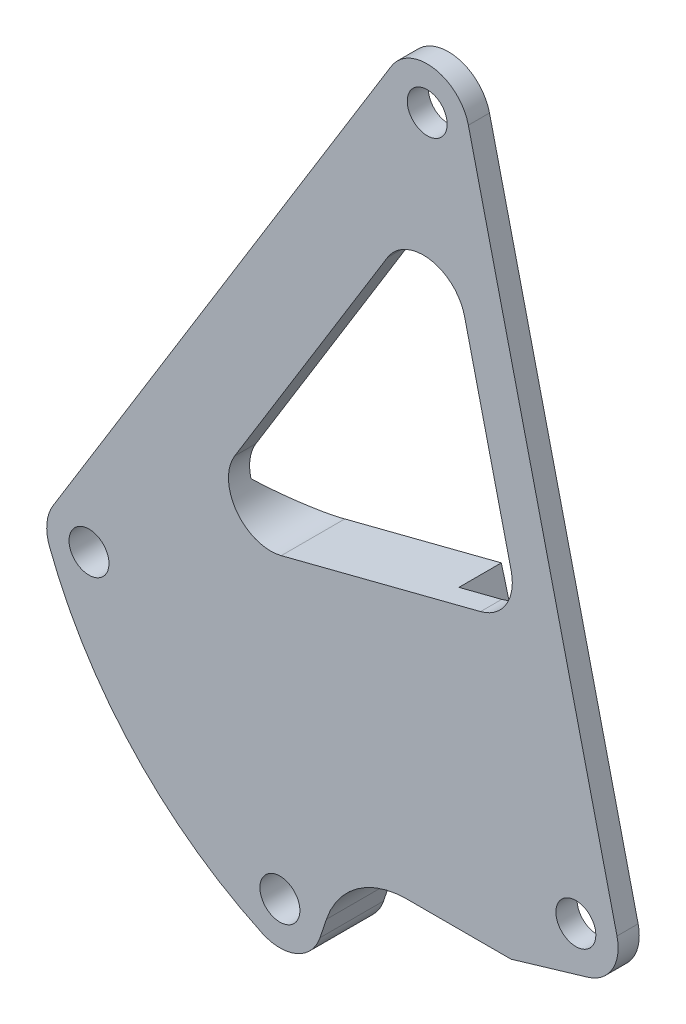
SolidWorks part; units mm, degrees
ref_plane "Front Plane" through (0, 0, 0) normal (0, 0, 1) x (1, 0, 0)
ref_plane "Top Plane" through (0, 0, 0) normal (0, 1, 0) x (1, 0, 0)
ref_plane "Right Plane" through (0, 0, 0) normal (1, 0, 0) x (0, 0, -1)
sketch "Sketch1" plane through (0, 0, 0) normal (0, 0, 1) x (1, 0, 0)
  circle A0 centre (0, 0) radius 3
  circle A1 centre (0, 0) radius 6.35
  dimension "D1" = 6
  dimension "D2" = 12.7
extrude "Boss-Extrude1" add sketch "Sketch1" along normal mid plane 6.3739
sketch "Sketch2" plane through (0, 0, 3.1869) normal (0, 0, 1) x (1, 0, 0)
  circle A0 centre (-28.6728, 30.8026) radius 3
  circle A1 centre (-28.6728, 30.8026) radius 6.35
  circle A2 centre (0, 0) radius 6.35 construction
  circle A3 centre (0, 0) radius 3 construction
  dimension "D1" = 28.6728
  dimension "D2" = 30.8026
extrude "Boss-Extrude2" add sketch "Sketch2" against normal blind 6.3739 separate body
sketch "Sketch3" plane through (0, 0, 0) normal (0, 0, 1) x (1, 0, 0)
  line L0 (-30.2527, 36.9529) -> (23.7075, 50.8147)
  line L1 (6.0215, -2.0158) -> (23.7075, 50.8147)
  line L2 (-28.6728, 30.8026) -> (0, 0) construction
  arc A0 (-34.6046, 28.5363) -> (-2.6848, -5.7545) centre (23.7075, 50.8147) ccw
  circle A1 centre (-28.6728, 30.8026) radius 6.35 construction
  circle A2 centre (0, 0) radius 6.35 construction
  circle A4 centre (-28.6728, 30.8026) radius 6.35
  arc A5 (-30.2527, 36.9529) -> (-34.6046, 28.5363) centre (-28.6728, 30.8026) ccw
  circle A6 centre (0, 0) radius 6.35
  arc A7 (-2.6848, -5.7545) -> (6.0215, -2.0158) centre (0, 0) ccw
  point P7 (5.1543, 3.7089)
  point P10 (22.8471, 50.0138)
  point P11 (22.8471, 50.0138)
  point P14 (-30.4587, 36.8963)
  dimension "D1" = 0
  dimension "D3" = 51.9755
  dimension "D2" = 0
extrude "Boss-Extrude3" add sketch "Sketch3" along normal mid plane 6.3739 contours L0 L1 A7 A0 A5
sketch "Sketch4" plane through (0, 0, 3.1869) normal (0, 0, 1) x (1, 0, 0)
  circle A0 centre (-28.6728, 30.8026) radius 3
  circle A1 centre (0, 0) radius 3
  point P6 (0, 0)
  dimension "D1" = 6
extrude "Cut-Extrude1" cut sketch "Sketch4" against normal through all both and the other way through all
sketch "Sketch5" plane through (0, 0, 3.1869) normal (0, 0, 1) x (1, 0, 0)
  line L0 (23.7075, 50.8147) -> (34.7142, 9.5397)
  line L1 (34.7142, 9.5397) -> (23.7075, 9.5397)
  line L2 (23.7075, 9.5397) -> (9.89, 9.5397)
  line L3 (6.0215, -2.0158) -> (23.7075, 50.8147) construction
  line L4 (9.89, 9.5397) -> (23.7075, 50.8147)
  line L5 (34.7142, 9.5397) -> (34.7142, 50.2676) construction
  dimension "D1" = 14.931
  dimension "D2" = 41.275
extrude "Boss-Extrude4" add sketch "Sketch5" against normal through all
fillet "Fillet1" radius 12.7 1 edges at (9.89, 9.5397, 0)
sketch "Sketch9" plane through (0, 0, 3.1869) normal (0, 0, 1) x (1, 0, 0)
  line L0 (-28.6728, 30.8026) -> (22.1272, 113.3526) construction
  line L1 (16.7192, 116.6806) -> (-34.0808, 34.1306)
  line L2 (27.5352, 110.0246) -> (-15.0246, 40.8648)
  line L3 (-30.2527, 36.9529) -> (23.7075, 50.8147) construction
  line L4 (-30.2527, 36.9529) -> (-15.0246, 40.8648)
  circle A0 centre (22.1272, 113.3526) radius 3
  circle A1 centre (-28.6728, 30.8026) radius 3 construction
  arc A2 (27.5352, 110.0246) -> (16.7192, 116.6806) centre (22.1272, 113.3526) ccw
  arc A3 (-30.2527, 36.9529) -> (-34.6046, 28.5363) centre (-28.6728, 30.8026) ccw construction
  arc A4 (-30.2527, 36.9529) -> (-34.0808, 34.1306) centre (-28.6728, 30.8026) ccw
  point P12 (-12.7142, 41.4583)
  dimension "D1" = 50.8
  dimension "D2" = 6
  dimension "D4" = 12.7
  dimension "D3" = 82.55
extrude "Boss-Extrude8" add sketch "Sketch9" along normal blind 3.175 separate body
sketch "Sketch10" plane through (0, 0, 3.1869) normal (0, 0, 1) x (1, 0, 0)
  line L0 (34.7142, 9.5397) -> (46.2553, 12.962)
  line L1 (42.6447, 25.138) -> (31.4406, 21.8156)
  line L2 (34.7142, 9.5397) -> (23.7075, 50.8147) construction
  line L3 (31.4406, 21.8156) -> (34.7142, 9.5397)
  circle A0 centre (44.45, 19.05) radius 3
  arc A1 (46.2553, 12.962) -> (42.6447, 25.138) centre (44.45, 19.05) ccw
  dimension "D1" = 6
  dimension "D2" = 12.7
  dimension "D3" = 44.45
  dimension "D4" = 19.05
extrude "Boss-Extrude9" add sketch "Sketch10" along normal blind 3.175 separate body
sketch "Sketch11" plane through (0, 0, 3.1869) normal (0, 0, 1) x (1, 0, 0)
  circle A1 centre (0, 0) radius 3
  circle A2 centre (0, 0) radius 3
  circle A3 centre (-28.6728, 30.8026) radius 3
  circle A4 centre (-28.6728, 30.8026) radius 3
  circle M3 centre (-28.6728, 30.8026) radius 3
  circle M4 centre (0, 0) radius 3
  line M5 (23.7075, 50.8147) -> (-30.2527, 36.9529)
  arc M6 (-30.2527, 36.9529) -> (-34.6046, 28.5363) centre (-28.6728, 30.8026) ccw
  arc M7 (-34.6046, 28.5363) -> (-2.6848, -5.7545) centre (23.7075, 50.8147) ccw
  arc M8 (-2.6848, -5.7545) -> (6.0215, -2.0158) centre (0, 0) ccw
  line M9 (6.0215, -2.0158) -> (6.9881, 0.8714)
  arc M10 (6.9881, 0.8714) -> (19.0312, 9.5397) centre (19.0312, -3.1603) cw
  line M11 (19.0312, 9.5397) -> (34.7142, 9.5397)
  line M12 (34.7142, 9.5397) -> (23.7075, 50.8147)
  dimension "D1" = 0
  dimension "D2" = 0
extrude "Boss-Extrude10" add sketch "Sketch11" along normal blind 3.175 contours M12 M5 M6 M7 M8 M9 M10 M11 M4 M3 region at (0.9554, 23.7249, 3.1869)
sketch "Sketch12" plane through (0, 0, 3.1869) normal (0, 0, -1) x (-1, 0, 0)
  line L0 (-50.6292, 20.5127) -> (-28.3064, 114.8153)
  line L1 (-24.1985, 104.6024) -> (-42.985, 25.2389)
  line L2 (15.0246, 40.8648) -> (-27.5352, 110.0246) construction
  line L3 (-42.6447, 25.138) -> (-31.4406, 21.8156) construction
  line L4 (-28.3064, 114.8153) -> (-24.1985, 104.6024)
  line L5 (-50.6292, 20.5127) -> (-42.985, 25.2389)
  arc A0 (-42.6447, 25.138) -> (-46.2553, 12.962) centre (-44.45, 19.05) ccw construction
  arc A1 (-16.7192, 116.6806) -> (-27.5352, 110.0246) centre (-22.1272, 113.3526) ccw construction
  dimension "D1" = 6.35
extrude "Boss-Extrude11" add sketch "Sketch12" against normal blind 3.175
sketch "Sketch14" plane through (0, 0, 6.3619) normal (0, 0, 1) x (1, 0, 0)
  line L0 (23.7075, 50.8147) -> (36.1728, 54.017)
  line L1 (42.985, 25.2389) -> (24.1985, 104.6024) construction
  line L2 (36.1728, 54.017) -> (42.9969, 25.2315)
  line L3 (42.9969, 25.2315) -> (31.4406, 21.8156)
  line L4 (31.4406, 21.8156) -> (23.7075, 50.8147)
  line L5 (23.7075, 50.8147) -> (-15.0246, 40.8648) construction
  point P5 (34.5103, 61.0403)
extrude "Boss-Extrude13" add sketch "Sketch14" against normal blind 3.175
fillet "Fillet2" radius 6.35 3 edges at (-15.0246, 40.8648, 4.7744) (24.1985, 104.6024, 4.7744) (36.1728, 54.017, 4.7744)
chamfer "Chamfer2" distance 6.35 angle 45 2 edges at (-32.441, 35.9137, 3.1869) (-15.0246, 40.8648, 3.1869)
